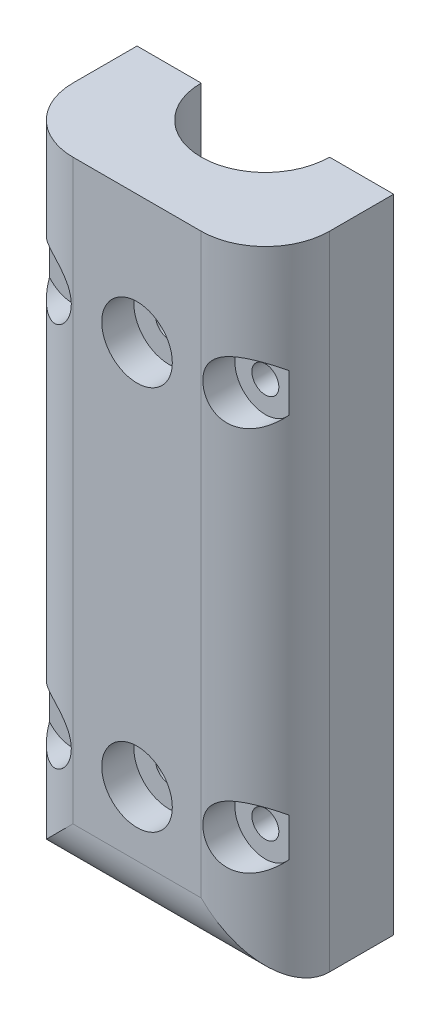
SolidWorks part; units mm, degrees
ref_plane "Front Plane" through (0, 0, 0) normal (0, 0, 1) x (1, 0, 0)
ref_plane "Top Plane" through (0, 0, 0) normal (0, 1, 0) x (1, 0, 0)
ref_plane "Right Plane" through (0, 0, 0) normal (1, 0, 0) x (0, 0, -1)
sketch "Sketch3" plane through (0, 0, 0) normal (0, 0, 1) x (1, 0, 0)
  line L1 (-20, -50) -> (20, -50)
  line L2 (-20, -50) -> (-20, 50)
  line L3 (-20, 50) -> (20, 50)
  line L4 (20, -50) -> (20, 50)
  line L5 (0, 50) -> (0, -50) construction
  line L6 (-20, 0) -> (20, 0) construction
  point P0 (0, 0)
  dimension "D1" = 40
  dimension "D2" = 100
extrude "Boss-Extrude1" add sketch "Sketch3" along normal blind 20
sketch "Sketch4" plane through (0, 50, 0) normal (0, 1, 0) x (1, 0, 0)
  line L0 (20, 0) -> (-20, 0) construction
  circle A0 centre (0, 0) radius 10
  dimension "D1" = 20
extrude "Cut-Extrude1" cut sketch "Sketch4" against normal through all
sketch "Sketch6" plane through (0, 0, 20) normal (0, 0, 1) x (1, 0, 0)
  line L0 (0, 0) -> (0, 30) construction
  line L1 (0, 0) -> (0, -30) construction
  line L2 (20, 50) -> (-20, 50) construction
  line L3 (-15, 50) -> (-15, -50) construction
  line L4 (-20, -50) -> (20, -50) construction
  line L5 (15, -50) -> (15, 50) construction
  circle A0 centre (0, 30) radius 2.1
  circle A1 centre (0, -30) radius 2.1
  circle A2 centre (0, 30) radius 5.5
  circle A3 centre (0, -30) radius 5.5
  circle A4 centre (-15, 30) radius 2.1
  circle A5 centre (-15, 30) radius 4.75
  circle A6 centre (-15, -30) radius 2.1
  circle A7 centre (-15, -30) radius 4.75
  circle A8 centre (15, -30) radius 4.75
  circle A9 centre (15, -30) radius 2.1
  circle A10 centre (15, 30) radius 4.75
  circle A11 centre (15, 30) radius 2.1
  dimension "D1" = 11
  dimension "D2" = 11
  dimension "D3" = 4.2
  dimension "D4" = 4.2
  dimension "D7" = 4.2
  dimension "D11" = 9.5
  dimension "D12" = 4.2
  dimension "D13" = 9.5
  dimension "D5" = 30
  dimension "D6" = 30
  dimension "D8" = 20
  dimension "D9" = 30
  dimension "D10" = 15
  dimension "D14" = 20
extrude "Cut-Extrude10" cut sketch "Sketch6" against normal blind 5
extrude "Cut-Extrude11" cut sketch "Sketch6<2>" against normal through all contours A4 | A0 | A11 | A6 | A1 | A9
sketch "Sketch6<2>" plane through (0, 0, 20) normal (0, 0, 1) x (1, 0, 0) same geometry as "Sketch6"
fillet "Fillet1" radius 10 3 edges at (0, -50, 20) (20, 0, 20) (-20, 0, 20)
